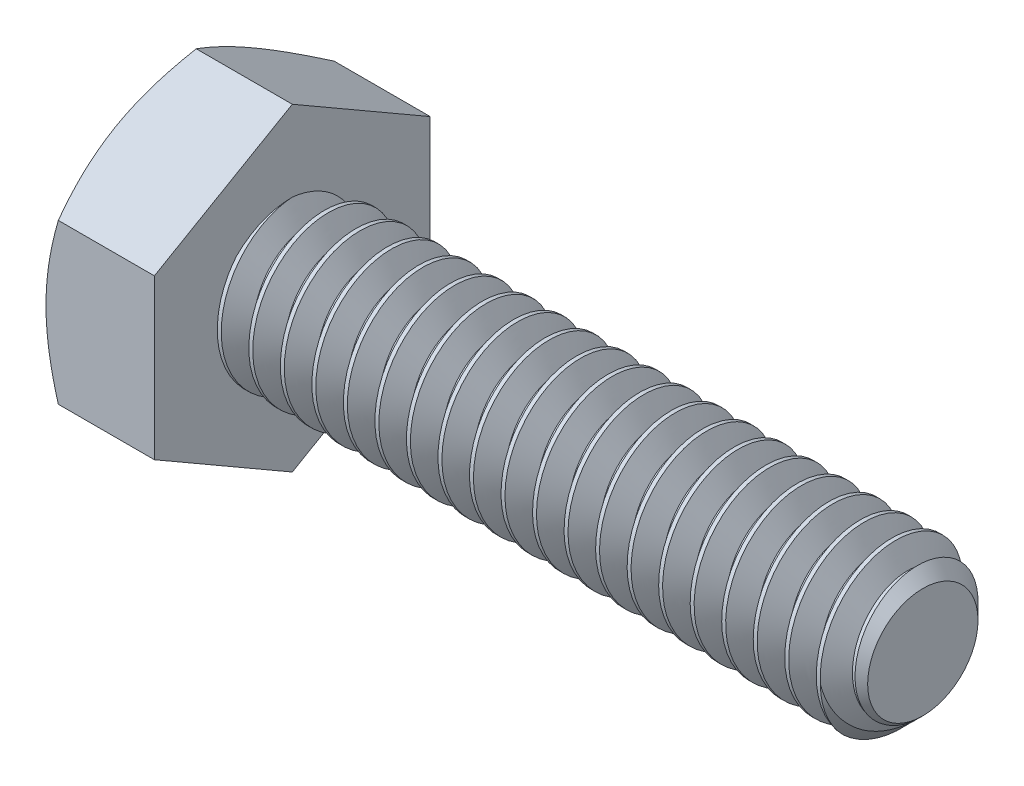
SolidWorks part; units mm, degrees
note: '?' marks a value the reader was unsure of.
ref_plane "Front Plane" through (0, 0, 0) normal (0, 0, 1) x (1, 0, 0)
ref_plane "Top Plane" through (0, 0, 0) normal (0, 1, 0) x (1, 0, 0)
ref_plane "Right Plane" through (0, 0, 0) normal (1, 0, 0) x (0, 0, -1)
sketch "Sketch1" plane through (0, 0, 0) normal (0, 0, 1) x (1, 0, 0)
  line L0 (-14.8828, 0) -> (14.8828, 0) construction
  line L1 (14.8828, 3.175) -> (14.8828, -3.175) construction
  line L2 (-10.5172, 5.5562) -> (-10.5172, -5.5562) construction
  line L3 (-14.8828, 5.5562) -> (-14.8828, -5.5562) construction
  point P9 (-10.5172, 0)
  point P10 (10.4378, -3.175)
  dimension "D1" = 4.445
  dimension "Screw Dia" = 6.35
  dimension "Hex" = 11.1125
  dimension "Head Ht" = 4.3656
  dimension "Screw Lenght" = 25.4
ref_plane "Plane2" through (14.8828, 0, 0) normal (1, 0, 0) x (0, 0, -1)
sketch "Sketch5" plane through (14.8828, 0, 0) normal (1, 0, 0) x (0, 0, -1)
  circle A0 centre (0, 0) radius 3.175
extrude "Boss-Extrude3" add sketch "Sketch5" against normal up to vertex (25.4 mm away) up to point (-10.5172, 0, 0)
sketch "Sketch9" plane through (14.8828, 0, 0) normal (1, 0, 0) x (0, 0, -1)
  circle A1 centre (0, 0) radius 3.175
  circle A2 centre (0, 0) radius 3.175
  dimension "D1" = 0
curve "Helix/Spiral1" pitch 1.27 height 26.67 turns 21 parameters "Pitch"=1.27
chamfer "Chamfer1" distance 0.9525 angle 45 1 edges at (14.8828, 0, -3.175)
sketch "Sketch10" plane through (0, 0, 0) normal (0, 0, 1) x (1, 0, 0)
  line L0 (14.8828, 3.175) -> (15.3591, 2.3501)
  line L1 (15.3591, 2.3501) -> (15.5178, 2.3501)
  line L2 (15.5178, 2.3501) -> (15.9941, 3.175)
  line L3 (14.8828, 3.175) -> (15.9941, 3.175)
  line L4 (15.4384, 3.175) -> (15.4384, 2.3501) construction
  line L5 (15.1209, 2.7626) -> (15.7559, 2.7626) construction
  dimension "D1" = 60
  dimension "D2" = 0.1588
  dimension "D3" = 0.635
sweep "Cut-Sweep1" cut profiles "Sketch10" path "Helix/Spiral1" align with end faces yes
sketch "Sketch6" plane through (-10.5172, 0, 0) normal (-1, 0, 0) x (0, 0, 1)
  line L0 (0, 5.5562) -> (0, -5.5562) construction
  line L1 (5.5562, 3.2079) -> (0, 6.4158)
  line L2 (0, 6.4158) -> (-5.5563, 3.2079)
  line L3 (-5.5563, 3.2079) -> (-5.5563, -3.2079)
  line L4 (-5.5563, -3.2079) -> (0, -6.4158)
  line L5 (0, -6.4158) -> (5.5562, -3.2079)
  line L6 (5.5562, -3.2079) -> (5.5562, 3.2079)
  circle A0 centre (0, 0) radius 5.5562 construction
extrude "Boss-Extrude4" add sketch "Sketch6" along normal up to vertex (4.3656 mm away) up to point (-14.8828, -5.5562, 0)
sketch "Sketch7" plane through (-14.8828, 0, 0) normal (-1, 0, 0) x (0, 0, 1)
  circle A0 centre (0, 0) radius 5.5562 construction
  circle A1 centre (0, 0) radius 5.5562
sketch "Sketch8" plane through (-14.8828, 0, 0) normal (-1, 0, 0) x (0, 0, 1)
  circle A0 centre (0, 0) radius 5.5562 construction
  circle A1 centre (0, 0) radius 5.5562
extrude "Cut-Extrude3" cut sketch "Sketch8" against normal through all draft 60 flip side to cut
sketch "Sketch12" plane through (-14.8828, 0, 0) normal (-1, 0, 0) x (0, 0, 1)
  line L0 (0, 4.2783) -> (0, 2.3892) construction
  line L1 (0.1667, 4.2783) -> (0.1667, 2.3892)
  line L2 (-0.1667, 4.2783) -> (-0.1667, 2.3892)
  line L3 (0, 3.175) -> (0, -3.175) construction
  arc A0 (0.1667, 4.2783) -> (-0.1667, 4.2783) centre (0, 4.2783) ccw
  arc A1 (-0.1667, 2.3892) -> (0.1667, 2.3892) centre (0, 2.3892) ccw
  circle A3 centre (0, 0) radius 2.2225 construction
  circle A4 centre (0, 0) radius 4.445 construction
  point P2 (0, 3.3337)
  dimension "D1" = 4.445
  dimension "D3" = 8.89
  dimension "D2" = 0.3334
extrude "Cut-Extrude4" cut sketch "Sketch12" against normal blind 0.254
pattern_circular "CirPattern1" count 6 over 360 about axis through (0, 0, 0) along (1, 0, 0) of "Cut-Extrude4"
ref_axis "Axis1" through (0, 0, 0) along (-1, 0, 0)?
equation "\"D2@Sketch10\" = \"Pitch@Helix/Spiral1\"*.125"
equation "\"D3@Sketch10\" = \"Pitch@Helix/Spiral1\"*.5"
equation "\"D3@Helix/Spiral1\" = \"Screw Lenght@Sketch1\"+\"Pitch@Helix/Spiral1\""
equation "\"D1@Chamfer1\" = \"Pitch@Helix/Spiral1\"*.75"
equation "\"D1@Sketch12\" = \"Hex@Sketch1\"*.4"
equation "\"D3@Sketch12\" = \"Hex@Sketch1\"*.8"
equation "\"D2@Sketch12\" = \"Hex@Sketch1\"*.03"
equation "\"D1@Sketch1\" = \"Pitch@Helix/Spiral1\"*3.5"
